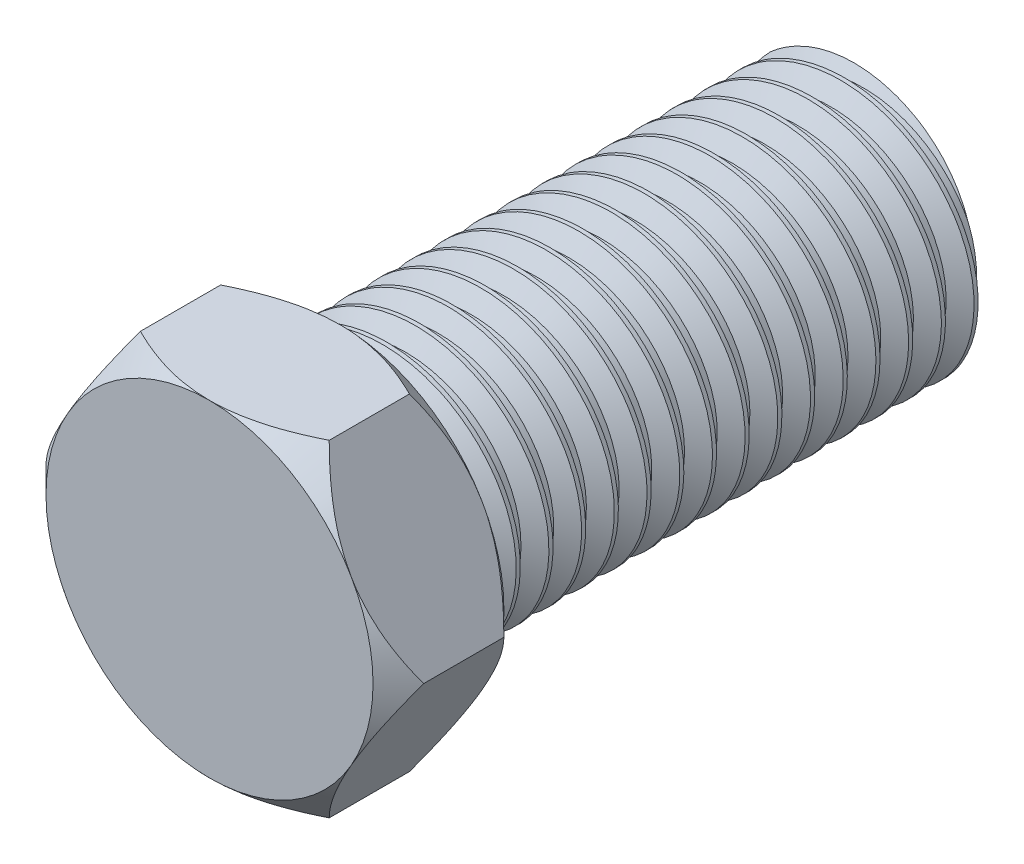
SolidWorks part; units mm, degrees
ref_plane "Front Plane" through (0, 0, 0) normal (0, 0, 1) x (1, 0, 0)
ref_plane "Top Plane" through (0, 0, 0) normal (0, 1, 0) x (1, 0, 0)
ref_plane "Right Plane" through (0, 0, 0) normal (1, 0, 0) x (0, 0, -1)
sketch "Sketch1" plane through (0, 0, 0) normal (0, 0, 1) x (1, 0, 0)
  line L0 (-1.4434, 0) -> (1.4434, 0) construction
  line L1 (1.4434, 0) -> (0.7217, 1.25)
  line L2 (0.7217, 1.25) -> (-0.7217, 1.25)
  line L3 (-0.7217, 1.25) -> (-1.4434, 0)
  line L4 (-1.4434, 0) -> (-0.7217, -1.25)
  line L5 (-0.7217, -1.25) -> (0.7217, -1.25)
  line L6 (0.7217, -1.25) -> (1.4434, 0)
  line L7 (0, 1.25) -> (0, -1.25) construction
  circle A0 centre (0, 0) radius 1.25
  circle A1 centre (0, 0) radius 1
  dimension "D1" = 2.5
  dimension "D2" = 2
extrude "Boss-Extrude1" add sketch "Sketch1" along normal blind 1 contours L1 L2 L3 L4 L5 L6
extrude "Boss-Extrude2" add sketch "Sketch1<3>" along normal up to next (1 mm away) and the other way blind 4 contours A1
sketch "Sketch1<3>" plane through (0, 0, 0) normal (0, 0, 1) x (1, 0, 0) same geometry as "Sketch1"
thread "Thread1" pitch 0.25 method cut profile "Thread Profile2" start angle 0, offset 0, length 0, pitch 0.25, diameter 2
ref_plane "Plane2" through (-1, 0, 0) normal (0, -1, 0) x (-1, 0, 0)
sketch "Thread Profile2" plane through (-1, 0, 0) normal (0, -1, 0) x (-1, 0, 0)
  line L0 (0, 0) -> (0, 0.25) construction
  line L11 (0, 0) -> (0, 0.2187)
  line L12 (0, 0.2187) -> (-0.1353, 0.1406)
  line L13 (-0.1353, 0.1406) -> (-0.1353, 0.0781)
  line L15 (-0.1353, 0.0781) -> (0, 0)
  line L17 (-0.1353, 0.1094) -> (0, 0.1094) construction
  point P2 (0, 0)
  dimension "Pitch" = 0.25
  dimension "Profile_Angle" = 60
  dimension "Profile_Land" = 0.0625
  dimension "Profile_Height" = 0.1353
extrude "Cut-Extrude3" cut sketch "Sketch1<8>" along normal blind 1 draft 45 flip side to cut contours A0
sketch "Sketch1<8>" plane through (0, 0, 0) normal (0, 0, 1) x (1, 0, 0) same geometry as "Sketch1"
ref_plane "Plane3" through (0, 0, 1) normal (0, 0, 1) x (1, 0, 0)
sketch "Sketch8" plane through (0, 0, 1) normal (0, 0, 1) x (1, 0, 0)
  circle A0 centre (0, 0) radius 1.25
  dimension "D1" = 2.5
extrude "Cut-Extrude4" cut sketch "Sketch8" against normal blind 1 draft 45 flip side to cut contours A0
ref_plane "Plane4" through (0, 0, -4) normal (0, 0, -1) x (-1, 0, 0)
sketch "Sketch9" plane through (0, 0, -4) normal (0, 0, -1) x (-1, 0, 0)
  line L0 (-1.4434, 0) -> (1.4434, 0) construction
  line L1 (0, 1.25) -> (0, -1.25) construction
  line L2 (-0.7217, 1.25) -> (0.7217, 1.25) construction
